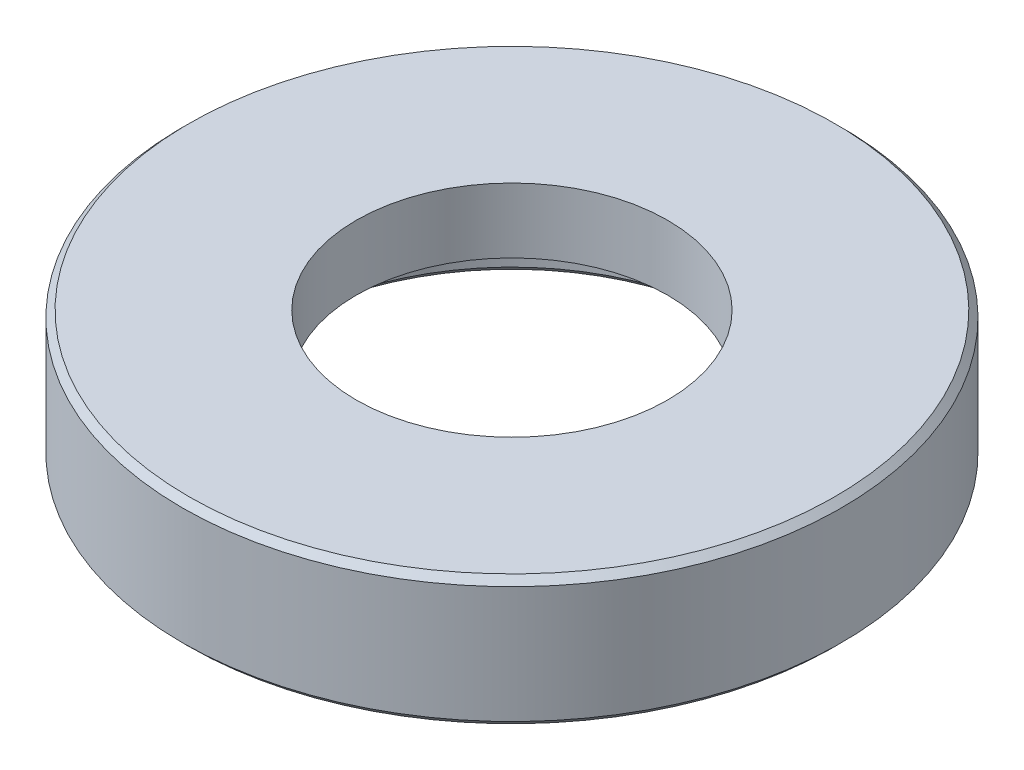
SolidWorks part; units mm, degrees
material "AISI 1045 Steel, cold drawn"
ref_plane "Front Plane" through (0, 0, 0) normal (0, 0, 1) x (1, 0, 0)
ref_plane "Top Plane" through (0, 0, 0) normal (0, 1, 0) x (1, 0, 0)
ref_plane "Right Plane" through (0, 0, 0) normal (1, 0, 0) x (0, 0, -1)
sketch "Sketch1" plane through (0, 0, 0) normal (0, 1, 0) x (1, 0, 0)
  circle A0 centre (0, 0) radius 6
  circle A1 centre (0, 0) radius 8.75
  circle A2 centre (0, 0) radius 12.7
extrude "Boss-Extrude1" add sketch "Sketch1" along normal blind 5 contours A2
extrude "Cut-Extrude1" cut sketch "Sketch1<3>" along normal up to surface (5 mm away) contours A0 up to face at (0, 5, 12.7)
sketch "Sketch1<3>" plane through (0, 0, 0) normal (0, 1, 0) x (1, 0, 0) same geometry as "Sketch1"
extrude "Cut-Extrude2" cut sketch "Sketch1<4>" along normal blind 2.5 contours A1 A0 region at (-8.5025, 0, 0)
sketch "Sketch1<4>" plane through (0, 0, 0) normal (0, 1, 0) x (1, 0, 0) same geometry as "Sketch1"
chamfer "Chamfer1" distance 0.25 angle 45 3 edges at (0, 5, 12.7) (0, 0, 8.75) (0, 0, 12.7)
